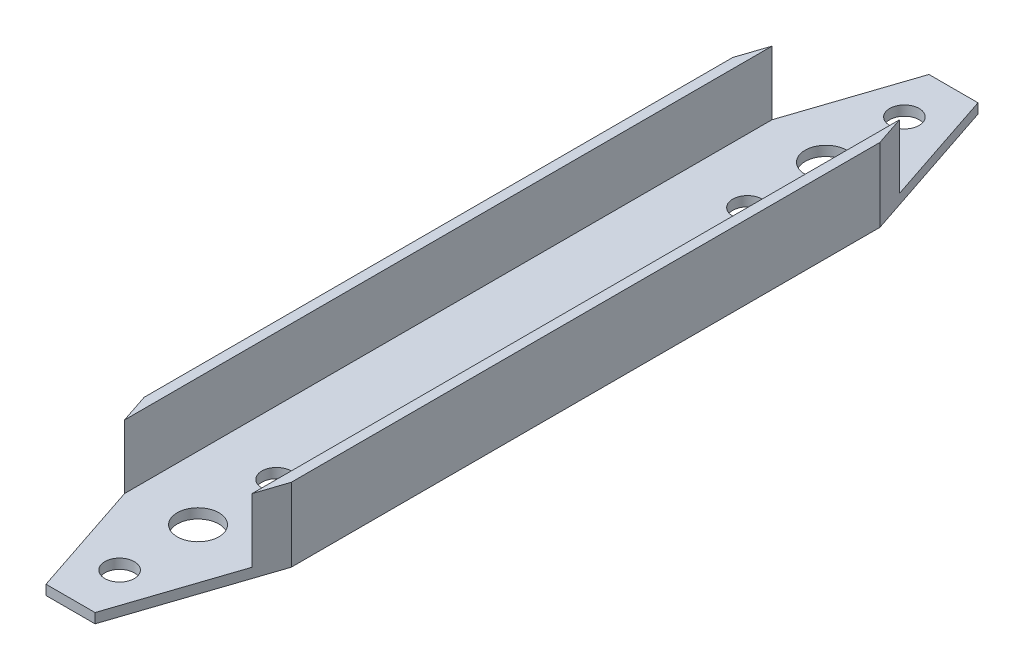
SolidWorks part; units mm, degrees
material "1060 slitina"
ref_plane "Front" through (0, 0, 0) normal (0, 0, 1) x (1, 0, 0)
ref_plane "Top" through (0, 0, 0) normal (0, 1, 0) x (1, 0, 0)
ref_plane "Right" through (0, 0, 0) normal (1, 0, 0) x (0, 0, -1)
sketch "Skica1" plane through (0, 0, 0) normal (0, 0, 1) x (1, 0, 0)
  line L0 (28, 15) -> (30, 15)
  line L1 (0, 0) -> (30, 0)
  line L2 (0, 0) -> (0, 15)
  line L3 (0, 15) -> (2, 15)
  line L4 (30, 0) -> (30, 15)
  line L6 (2, 15) -> (2, 2)
  line L7 (2, 2) -> (28, 2)
  line L8 (28, 15) -> (28, 2)
  dimension "D1" = 30
  dimension "D2" = 15
  dimension "D3" = 2
  dimension "D4" = 2
  dimension "D5" = 2
extrude "Přidat vysunutím1" add sketch "Skica1" along normal blind 180
sketch "Skica2" plane through (0, 2, 0) normal (0, 1, 0) x (1, 0, 0)
  line L0 (15, -180) -> (15, 0) construction
  line L1 (28, -180) -> (2, -180) construction
  line L2 (28, 0) -> (2, 0) construction
  line L3 (15.71, -154) -> (50015.71, -154) construction
  line L5 (2, -90) -> (50002, -90) construction
  line L6 (2, -180) -> (2, 0) construction
  line L7 (28, -180) -> (28, 0) construction
  circle A0 centre (15, -170) radius 3
  circle A1 centre (15, -154) radius 4.25
  circle A2 centre (15, -138) radius 3
  circle A3 centre (15, -42) radius 3
  circle A4 centre (15, -26) radius 4.25
  circle A5 centre (15, -10) radius 3
  point P20 (2, -90)
  point P23 (28, -90)
  dimension "D1" = 26
  dimension "D2" = 8.5
  dimension "D3" = 6
  dimension "D4" = 16
extrude "Odebrat vysunutím1" cut sketch "Skica2" against normal up to next
sketch "Skica3" plane through (0, 0, 0) normal (0, -1, 0) x (1, 0, 0)
  line L0 (15, 180) -> (15, -49820) construction
  line L3 (0, 0) -> (30, 0) construction
  line L4 (0, 90) -> (50000, 90) construction
  line L5 (30, 180) -> (30, 0) construction
  line L6 (0, 180) -> (0, 0) construction
  line L7 (30, 180) -> (20, 180)
  line L8 (30, 150) -> (30, 180)
  line L9 (20, 180) -> (30, 150)
  line L10 (0, 180) -> (30, 180) construction
  line L11 (0, 0) -> (10, 0)
  line L12 (0, 30) -> (0, 0)
  line L13 (10, 180) -> (0, 150)
  line L14 (0, 150) -> (0, 180)
  line L15 (0, 180) -> (10, 180)
  line L16 (10, 0) -> (0, 30)
  line L17 (20, 0) -> (30, 30)
  line L18 (30, 30) -> (30, 0)
  line L19 (30, 0) -> (20, 0)
  point P2 (15, 180)
  point P5 (15, 0)
  point P9 (0, 90)
  point P15 (30, 90)
  dimension "D6" = 10
  dimension "D7" = 30
extrude "Odebrat vysunutím2" cut sketch "Skica3" against normal up to surface (15 mm away) up to face at (29, 15, 90)
fillet "Zaoblit1" [suppressed] radius 3
